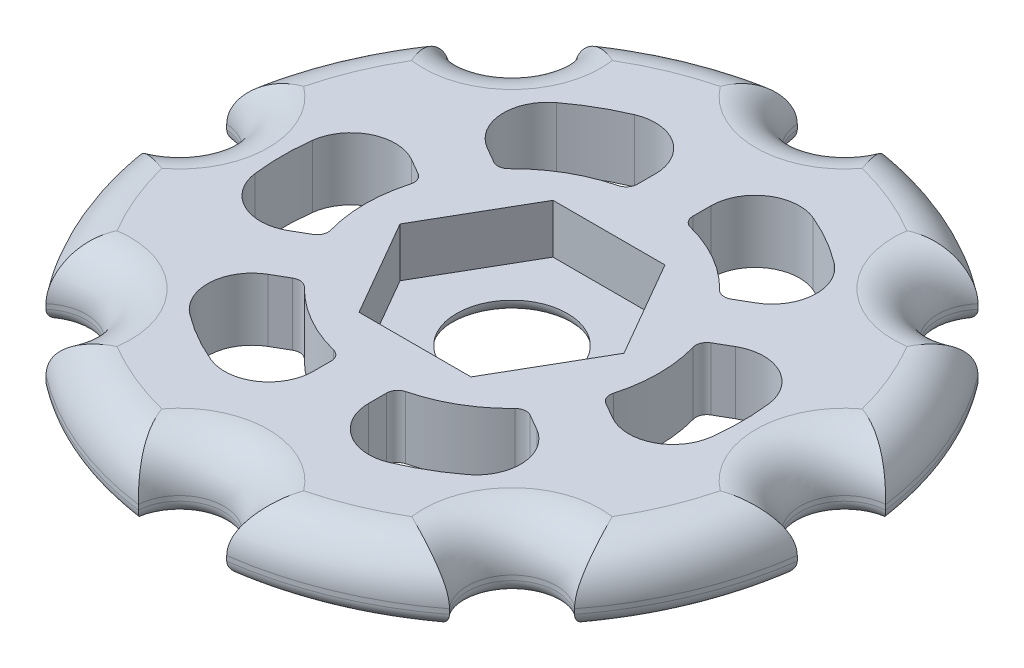
SolidWorks part; units mm, degrees
material "ABS"
ref_plane "Front Plane" through (0, 0, 0) normal (0, 0, 1) x (1, 0, 0)
ref_plane "Top Plane" through (0, 0, 0) normal (0, 1, 0) x (1, 0, 0)
ref_plane "Right Plane" through (0, 0, 0) normal (1, 0, 0) x (0, 0, -1)
sketch "Sketch2" plane through (0, 0, 0) normal (0, 0, 1) x (1, 0, 0)
  line L0 (0, 3.5814) -> (0, 0)
  line L3 (19.05, 0) -> (0, 0)
  line L4 (0, 0) -> (0, 4.8449) construction
  line L5 (0, 3.5814) -> (19.05, 3.5814)
  line L6 (19.05, 3.5814) -> (19.05, 0)
  dimension "D3" = 3.5814
  dimension "D4" = 19.05
revolve "Revolve1" add sketch "Sketch2" angle 360 about L4
sketch "Sketch3" plane through (0, 3.5814, 0) normal (0, 1, 0) x (1, 0, 0)
  line L1 (3.2079, 5.5562) -> (-3.2079, 5.5562)
  line L2 (-3.2079, 5.5562) -> (-6.4158, 0)
  line L3 (-6.4158, 0) -> (-3.2079, -5.5562)
  line L4 (-3.2079, -5.5562) -> (3.2079, -5.5562)
  line L5 (3.2079, -5.5562) -> (6.4158, 0)
  line L6 (6.4158, 0) -> (3.2079, 5.5562)
  circle A0 centre (0, 0) radius 5.5562 construction
  dimension "D1" = 11.1125
extrude "Cut-Extrude1" cut sketch "Sketch3" against normal blind 2.8194 contours L6 L1 L2 L3 L4 L5
sketch "Sketch4" plane through (0, 0.762, 0) normal (0, 1, 0) x (1, 0, 0)
  circle A0 centre (0, 0) radius 3.175
  dimension "D1" = 6.35
extrude "Cut-Extrude2" cut sketch "Sketch4" against normal through all contours A0
sketch "Sketch9" plane through (0, 0, 0) normal (0, -1, 0) x (-1, 0, 0)
  point P0 (0, 0)
hole_wizard "CSK for #10 Flat Head Machine Screw (100)1" [suppressed] positions "Sketch10" profile "Sketch11" countersink size "#10" standard "ANSI Inch"
sketch "Sketch10" plane through (0, 0, 0) normal (0, -1, 0) x (-1, 0, 0)
  point P0 (0, 0)
sketch "Sketch11" plane through (0, 0, 0) normal (1, 0, 0) x (0, 0, -1)
  line L0 (0, 0) -> (0, 3.5814)
  line L1 (0, 3.5814) -> (2.8067, 3.5814)
  line L2 (2.8067, 3.5814) -> (2.8067, 1.7477)
  line L3 (2.8067, 1.7477) -> (4.8895, 0)
  line L5 (4.8895, 0) -> (0, 0)
  line L6 (-2.8067, 1.7477) -> (-4.8895, 0) construction
  line L11 (0, -6.35) -> (0, 107.95) construction
  dimension "Thru Hole Dia." = 5.6134
  dimension "Thru Hole Depth" = 3.5814
  dimension "Near C'Sink Dia." = 9.779
  dimension "Near C'Sink Angle" = 100
sketch "Sketch5" plane through (0, 0, 0) normal (0, 0, 1) x (1, 0, 0)
  line L0 (0, 13.5532) -> (0, -13.8993) construction
sketch "Sketch6" plane through (0, 3.5814, 0) normal (0, 1, 0) x (1, 0, 0)
  line L0 (0, 24.6392) -> (0, -26.1994) construction
  arc A0 (-2.5343, 18.8807) -> (2.5343, 18.8807) centre (0, 19.05) ccw
  circle A1 centre (0, 0) radius 19.05 construction
  arc A2 (11.5586, 15.1427) -> (15.1427, 11.5586) centre (13.4704, 13.4704) ccw
  arc A3 (18.8807, 2.5343) -> (18.8807, -2.5343) centre (19.05, 0) ccw
  arc A4 (15.1427, -11.5586) -> (11.5586, -15.1427) centre (13.4704, -13.4704) ccw
  arc A5 (2.5343, -18.8807) -> (-2.5343, -18.8807) centre (0, -19.05) ccw
  arc A6 (-11.5586, -15.1427) -> (-15.1427, -11.5586) centre (-13.4704, -13.4704) ccw
  arc A7 (-18.8807, -2.5343) -> (-18.8807, 2.5343) centre (-19.05, 0) ccw
  arc A8 (-15.1427, 11.5586) -> (-11.5586, 15.1427) centre (-13.4704, 13.4704) ccw
  circle A9 centre (0, 0) radius 19.05
  point P31 (0, 0)
  circle M8 centre (0, 0) radius 19.05
  dimension "D1" = 2.54
  dimension "D4" = 38.1
  dimension "D3" = 19.05
  dimension "D2" = 8
extrude "Cut-Extrude5" cut sketch "Sketch6" against normal through all contours A8 M8 | A7 M8 | A6 M8 | L0 A5 M8 | A5 L0 A9 | A4 M8 | A3 M8 | A2 M8 | L0 A0 M8 | L0 A9 A0
fillet "Fillet1" radius 2.54 16 edges at (0, 3.5814, 16.51) (11.6743, 3.5814, 11.6743) (16.51, 3.5814, 0) (11.6743, 3.5814, -11.6743) (0, 3.5814, -16.51) (-7.2901, 3.5814, 17.5999) (7.2901, 3.5814, 17.5999) (17.5999, 3.5814, 7.2901) (17.5999, 3.5814, -7.2901) (7.2901, 3.5814, -17.5999) (-7.2901, 3.5814, -17.5999) (-11.6743, 3.5814, -11.6743) (-17.5999, 3.5814, -7.2901) (-16.51, 3.5814, 0) (-17.5999, 3.5814, 7.2901) (-11.6743, 3.5814, 11.6743)
fillet "Fillet2" radius 0.762 17 edges at (0, 0, 3.175) (-17.5999, 0, 7.2901) (-11.6743, 0, 11.6743) (-7.2901, 0, 17.5999) (0, 0, 16.51) (7.2901, 0, 17.5999) (11.6743, 0, 11.6743) (17.5999, 0, 7.2901) (16.51, 0, 0) (17.5999, 0, -7.2901) (11.6743, 0, -11.6743) (7.2901, 0, -17.5999) (0, 0, -16.51) (-7.2901, 0, -17.5999) (-11.6743, 0, -11.6743) (-17.5999, 0, -7.2901) (-16.51, 0, 0)
sketch "Sketch7" plane through (0, 0, 0) normal (0, -1, 0) x (1, 0, 0)
  line L3 (-1.5875, 8.2626) -> (-1.5875, 13.0803)
  line L4 (1.5875, 8.2626) -> (1.5875, 13.0803)
  line L5 (7.9494, 2.7565) -> (12.1216, 5.1653)
  line L6 (6.3619, 5.5061) -> (10.5341, 7.9149)
  line L7 (6.3619, -5.5061) -> (10.5341, -7.9149)
  line L8 (7.9494, -2.7565) -> (12.1216, -5.1653)
  line L9 (-1.5875, -8.2626) -> (-1.5875, -13.0803)
  line L10 (1.5875, -8.2626) -> (1.5875, -13.0803)
  line L11 (-7.9494, -2.7565) -> (-12.1216, -5.1653)
  line L12 (-6.3619, -5.5061) -> (-10.5341, -7.9149)
  line L13 (-6.3619, 5.5061) -> (-10.5341, 7.9149)
  line L14 (-7.9494, 2.7565) -> (-12.1216, 5.1653)
  line L15 (-1.5875, 10.6714) -> (1.5875, 10.6714) construction
  circle A0 centre (0, 0) radius 13.1762
  circle A2 centre (0, 0) radius 8.4138
  point P30 (0, 0)
  point P31 (0, 0)
  dimension "D1" = 26.3525
  dimension "D3" = 4.7625
  dimension "D2" = 3.175
  dimension "D4" = 6
extrude "Cut-Extrude6" cut sketch "Sketch7" against normal through all
fillet "Fillet3" radius 2.54 12 edges at (1.5875, 1.7907, -13.0803) (10.5341, 1.7907, -7.9149) (-1.5875, 1.7907, -13.0803) (-10.5341, 1.7907, -7.9149) (-12.1216, 1.7907, -5.1653) (-12.1216, 1.7907, 5.1653) (-10.5341, 1.7907, 7.9149) (-1.5875, 1.7907, 13.0803) (12.1216, 1.7907, 5.1653) (12.1216, 1.7907, -5.1653) (1.5875, 1.7907, 13.0803) (10.5341, 1.7907, 7.9149)
fillet "Fillet14" radius 0.635 12 edges at (6.3619, 1.7907, 5.5061) (1.5875, 1.7907, 8.2626) (-1.5875, 1.7907, 8.2626) (-6.3619, 1.7907, 5.5061) (-7.9494, 1.7907, 2.7565) (-7.9494, 1.7907, -2.7565) (-1.5875, 1.7907, -8.2626) (-6.3619, 1.7907, -5.5061) (1.5875, 1.7907, -8.2626) (6.3619, 1.7907, -5.5061) (7.9494, 1.7907, 2.7565) (7.9494, 1.7907, -2.7565)
